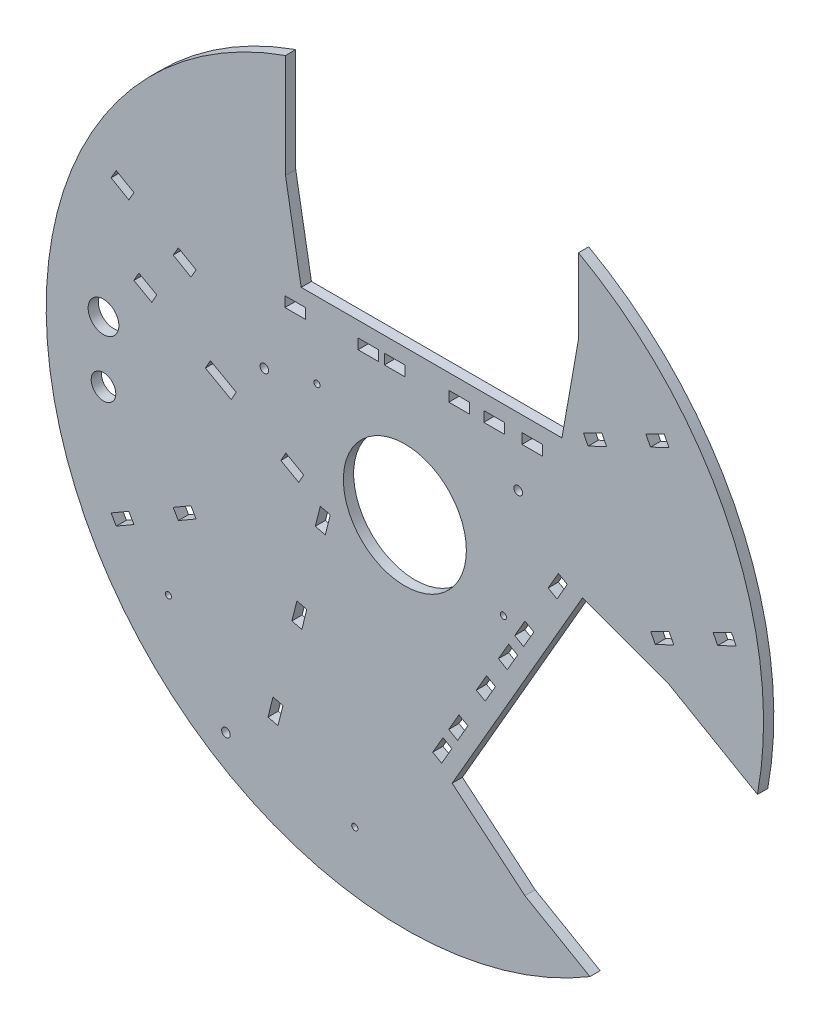
SolidWorks part; units mm, degrees
material "Balsa"
ref_plane "Plan de face" through (0, 0, 0) normal (0, 0, 1) x (1, 0, 0)
ref_plane "Plan de dessus" through (0, 0, 0) normal (0, 1, 0) x (1, 0, 0)
ref_plane "Plan de droite" through (0, 0, 0) normal (1, 0, 0) x (0, 0, -1)
sketch "Esquisse1" plane through (0, 0, 0) normal (0, 0, 1) x (1, 0, 0)
  circle A0 centre (0, 0) radius 175
  dimension "D1" = 350
extrude "Boss.-Extru.1" add sketch "Esquisse1" along normal blind 5
sketch "Esquisse2" plane through (0, 0, 0) normal (0, 0, -1) x (-1, 0, 0)
  line L0 (58.2408, 114.332) -> (58.2408, 213.8766)
  line L1 (58.2408, 213.8766) -> (-84.6817, 213.8766)
  line L2 (-84.6817, 213.8766) -> (-84.6817, 116.5135)
  line L3 (0, 0) -> (-290.6498, 0) construction
  line L4 (-84.6817, 116.5135) -> (-76.6366, 70.8876)
  line L5 (-76.6366, 70.8876) -> (50.5804, 70.8876)
  line L6 (50.5804, 70.8876) -> (58.2408, 114.332)
  line L7 (-128.1349, -6.728) -> (-214.343, -56.5003)
  line L8 (-214.343, -56.5003) -> (-142.8818, -180.2748)
  line L9 (-142.8818, -180.2748) -> (-58.5628, -131.5932)
  line L10 (-58.5628, -131.5932) -> (-23.0722, -101.8131)
  line L11 (-23.0722, -101.8131) -> (-86.6807, 8.3601)
  line L12 (-86.6807, 8.3601) -> (-128.1349, -6.728)
  point P16 (0, 0)
  point P43 (0, 0)
  dimension "D5" = 142.989
  dimension "D6" = 99.5446
  dimension "D1" = 127.217
  dimension "D2" = 100
  dimension "D3" = 100
  dimension "D4" = 142.9225
  dimension "D7" = 70.8876
  dimension "D8" = 50.5804
  dimension "D10" = 120
  dimension "D9" = 2
extrude "Enlèv. mat.-Extru.1" cut sketch "Esquisse2" against normal blind 5
sketch "Esquisse3" plane through (0, 0, 5) normal (0, 0, 1) x (1, 0, 0)
  line L0 (0, 0) -> (0, 103.8673) construction
  line L1 (-49.3567, -7.7578) -> (-58.0775, -2.8643)
  line L2 (-49.3567, -7.7578) -> (-51.8034, -12.1183)
  line L3 (-58.0775, -2.8643) -> (-60.5243, -7.2247)
  line L4 (-51.8034, -12.1183) -> (-60.5243, -7.2247)
  line L5 (-82.2991, 10.7274) -> (-94.8707, 17.7817)
  line L6 (-82.2991, 10.7274) -> (-84.7459, 6.3669)
  line L7 (-94.8707, 17.7817) -> (-97.3175, 13.4213)
  line L8 (-84.7459, 6.3669) -> (-97.3175, 13.4213)
  line L9 (-121.0332, 32.4625) -> (-129.754, 37.356)
  line L10 (-121.0332, 32.4625) -> (-123.48, 28.1021)
  line L11 (-129.754, 37.356) -> (-132.2008, 32.9956)
  line L12 (-123.48, 28.1021) -> (-132.2008, 32.9956)
  line L13 (-36.4119, -18.1392) -> (-38.8398, -27.84)
  line L14 (-36.4119, -18.1392) -> (-41.2623, -16.9253)
  line L15 (-38.8398, -27.84) -> (-43.6902, -26.6261)
  line L16 (0, 0) -> (104.6701, 42.2895) construction
  line L17 (-41.2623, -16.9253) -> (-43.6902, -26.6261)
  line L18 (-47.8487, -63.8364) -> (-50.2765, -73.5372)
  line L19 (-47.8487, -63.8364) -> (-52.6991, -62.6224)
  line L20 (-50.2765, -73.5372) -> (-55.1269, -72.3233)
  line L21 (-52.6991, -62.6224) -> (-55.1269, -72.3233)
  line L22 (-59.4765, -110.2968) -> (-61.9044, -119.9976)
  line L23 (-59.4765, -110.2968) -> (-64.3269, -109.0829)
  line L24 (-61.9044, -119.9976) -> (-66.7548, -118.7837)
  line L25 (-64.3269, -109.0829) -> (-66.7548, -118.7837)
  line L26 (62.9144, -18.0042) -> (58.5843, -15.5042)
  line L27 (62.9144, -18.0042) -> (57.9144, -26.6645)
  line L28 (58.5843, -15.5042) -> (53.5843, -24.1645)
  line L29 (57.9144, -26.6645) -> (53.5843, -24.1645)
  line L30 (39.8511, -47.9511) -> (44.1813, -50.4511)
  line L31 (39.8511, -47.9511) -> (34.8511, -56.6113)
  line L32 (44.1813, -50.4511) -> (39.1813, -59.1113)
  line L33 (34.8511, -56.6113) -> (39.1813, -59.1113)
  line L34 (18.5843, -84.7863) -> (22.9144, -87.2863)
  line L35 (18.5843, -84.7863) -> (13.5843, -93.4465)
  line L36 (22.9144, -87.2863) -> (17.9144, -95.9465)
  line L37 (13.5843, -93.4465) -> (17.9144, -95.9465)
  line L38 (23.0722, -101.8131) -> (86.6807, 8.3601) construction
  line L40 (67.1551, 63.3876) -> (57.1551, 63.3876)
  line L41 (67.1551, 63.3876) -> (67.1551, 58.3876)
  line L42 (67.1551, 58.3876) -> (57.1551, 58.3876)
  line L43 (57.1551, 63.3876) -> (57.1551, 58.3876)
  line L44 (-12.8449, 63.3876) -> (-22.8449, 63.3876)
  line L45 (-12.8449, 63.3876) -> (-12.8449, 58.3876)
  line L46 (-12.8449, 58.3876) -> (-22.8449, 58.3876)
  line L47 (-22.8449, 63.3876) -> (-22.8449, 58.3876)
  line L48 (31.4441, 63.3876) -> (21.4441, 63.3876)
  line L49 (31.4441, 63.3876) -> (31.4441, 58.3876)
  line L50 (31.4441, 58.3876) -> (21.4441, 58.3876)
  line L51 (21.4441, 63.3876) -> (21.4441, 58.3876)
  line L52 (76.6366, 70.8876) -> (-50.5804, 70.8876) construction
  line B0 (122.1484, 6.3102) -> (119.9636, 10.8076)
  line B1 (128.9584, 15.1772) -> (119.9636, 10.8076)
  line B2 (131.1432, 10.6797) -> (122.1484, 6.3102)
  line B3 (131.1432, 10.6797) -> (128.9584, 15.1772)
  line B4 (159.3791, 29.9551) -> (150.3842, 25.5855)
  line B5 (152.569, 21.0881) -> (150.3842, 25.5855)
  line B6 (161.5639, 25.4577) -> (159.3791, 29.9551)
  line B7 (161.5639, 25.4577) -> (152.569, 21.0881)
  line B8 (126.6073, 97.4163) -> (117.6125, 93.0467)
  line B9 (126.6073, 97.4163) -> (128.7921, 92.9189)
  line B10 (117.6125, 93.0467) -> (119.7973, 88.5493)
  line B11 (128.7921, 92.9189) -> (119.7973, 88.5493)
  line B12 (96.1867, 82.6383) -> (98.3714, 78.1409)
  line B13 (96.1867, 82.6383) -> (87.1918, 78.2688)
  line B14 (98.3714, 78.1409) -> (89.3766, 73.7714)
  line B15 (87.1918, 78.2688) -> (89.3766, 73.7714)
  line B16 (87.1918, 78.2688) -> (104.6701, 42.2895) construction
  dimension "D1" = 112.6276
  dimension "D2" = 68
  dimension "D3" = 5
  dimension "D4" = 5
  dimension "D5" = 30.9185
  dimension "D6" = 7.4
  dimension "D7" = 5
  dimension "D8" = 10
  dimension "D9" = 10
  dimension "D10" = 10
  dimension "D11" = 10
  dimension "D12" = 5
  dimension "D13" = 10
  dimension "D14" = 32.5336
  dimension "D15" = 10
  dimension "D16" = 27.4664
  dimension "D17" = 7.5
  dimension "D18" = 10
sketch_block_instance "Bloc1-1"
sketch_block "Bloc1" parameters "D1"=5, "D2"=23.8202, "D3"=40, "D4"=10, "D5"=10, "D6"=5
extrude "Enlèv. mat.-Extru.2" cut sketch "Esquisse3" against normal blind 10
sketch "Esquisse4" plane through (0, 0, 0) normal (0, 0, -1) x (-1, 0, 0)
  line L0 (42.8627, 33.9844) -> (-48.07, -18.5156) construction
  line L1 (42.8627, 33.9844) -> (115.3627, -91.5893) construction
  line L2 (-48.07, -18.5156) -> (24.43, -144.0893) construction
  line L3 (115.3627, -91.5893) -> (24.43, -144.0893) construction
  line L4 (-23.0722, -101.8131) -> (-86.6807, 8.3601) construction
  circle A0 centre (115.3627, -91.5893) radius 1.5
  circle A1 centre (24.43, -144.0893) radius 1.5
  circle A2 centre (-48.07, -18.5156) radius 1.5
  circle A3 centre (42.8627, 33.9844) radius 1.5
  dimension "D1" = 3
  dimension "D2" = 105
  dimension "D3" = 145
  dimension "D4" = 20
  dimension "D5" = 8
extrude "Enlèv. mat.-Extru.3" cut sketch "Esquisse4" against normal blind 10
sketch "Esquisse5" plane through (0, 0, 0) normal (0, 0, -1) x (-1, 0, 0)
  line L0 (132.1784, -70.1252) -> (134.6784, -65.7951)
  line L1 (132.1784, -70.1252) -> (140.8387, -75.1252)
  line L2 (134.6784, -65.7951) -> (143.3387, -70.7951)
  line L3 (140.8387, -75.1252) -> (143.3387, -70.7951)
  line L4 (110.5278, -57.6252) -> (113.0278, -53.2951)
  line L5 (110.5278, -57.6252) -> (101.8675, -52.6252)
  line L6 (113.0278, -53.2951) -> (104.3675, -48.2951)
  line L7 (101.8675, -52.6252) -> (104.3675, -48.2951)
  line L8 (134.6784, 65.7951) -> (132.1784, 70.1252)
  line L9 (134.6784, 65.7951) -> (143.3387, 70.7951)
  line L10 (132.1784, 70.1252) -> (140.8387, 75.1252)
  line L11 (143.3387, 70.7951) -> (140.8387, 75.1252)
  line L12 (110.5278, 57.6252) -> (113.0278, 53.2951)
  line L13 (110.5278, 57.6252) -> (101.8675, 52.6252)
  line L14 (113.0278, 53.2951) -> (104.3675, 48.2951)
  line L15 (101.8675, 52.6252) -> (104.3675, 48.2951)
  line L16 (134.6784, 65.7951) -> (113.0278, 53.2951) construction
  line L17 (143.3387, 70.7951) -> (104.3675, 48.2951) construction
  line L18 (143.3387, -70.7951) -> (104.3675, -48.2951) construction
  dimension "D1" = 10
  dimension "D2" = 115
  dimension "D3" = 25
  dimension "D4" = 25
  dimension "D5" = 5
  dimension "D6" = 115
extrude "Enlèv. mat.-Extru.4" cut sketch "Esquisse5" against normal blind 10
sketch "Esquisse6" plane through (0, 0, 5) normal (0, 0, 1) x (1, 0, 0)
  line L0 (20.7319, -91.0665) -> (84.2319, 18.9187) construction
  line L1 (25.7319, -82.4063) -> (30.7319, -73.746)
  line L2 (25.7319, -82.4063) -> (21.4018, -79.9063)
  line L3 (30.7319, -73.746) -> (26.4018, -71.246)
  line L4 (21.4018, -79.9063) -> (26.4018, -71.246)
  line L5 (49.9819, -40.4041) -> (54.9819, -31.7438)
  line L6 (49.9819, -40.4041) -> (45.6518, -37.9041)
  line L7 (54.9819, -31.7438) -> (50.6518, -29.2438)
  line L8 (45.6518, -37.9041) -> (50.6518, -29.2438)
  line L9 (52.4819, -36.0739) -> (43.8216, -31.0739) construction
  line L10 (58.5, 63.3876) -> (-68.5, 63.3876) construction
  line L11 (48.5, 63.3876) -> (38.5, 63.3876)
  line L12 (48.5, 63.3876) -> (48.5, 58.3876)
  line L14 (74.9018, 12.7584) -> (69.9018, 4.0982)
  line L15 (74.2319, 1.5982) -> (69.9018, 4.0982)
  line L16 (79.2319, 10.2584) -> (74.9018, 12.7584)
  line L17 (79.2319, 10.2584) -> (74.2319, 1.5982)
  line L20 (57.9144, -26.6645) -> (62.9144, -18.0042) construction
  line L21 (38.5, 63.3876) -> (38.5, 58.3876)
  line L22 (48.5, 58.3876) -> (38.5, 58.3876)
  line L23 (0, 63.3876) -> (-10, 63.3876)
  line L24 (0, 63.3876) -> (0, 58.3876)
  line L25 (-10, 63.3876) -> (-10, 58.3876)
  line L26 (0, 58.3876) -> (-10, 58.3876)
  line L27 (-5, 63.3876) -> (-5, 53.3876) construction
  line L29 (-58.5, 58.3876) -> (-48.5, 58.3876)
  line L30 (-48.5, 63.3876) -> (-48.5, 58.3876)
  line L31 (-58.5, 63.3876) -> (-58.5, 58.3876)
  line L32 (-58.5, 63.3876) -> (-48.5, 63.3876)
  line L33 (67.1551, 63.3876) -> (57.1551, 63.3876) construction
  dimension "D1" = 127
  dimension "D2" = 10
  dimension "D3" = 10
  dimension "D4" = 5
  dimension "D5" = 5
  dimension "D6" = 10
  dimension "D7" = 127
  dimension "D8" = 10
  dimension "D9" = 10
  dimension "D10" = 5
  dimension "D11" = 10
  dimension "D12" = 5
extrude "Enlèv. mat.-Extru.5" cut sketch "Esquisse6" against normal blind 5
hole_wizard "Trou taraudé M51" positions "Esquisse8" profile "Esquisse9" tap size "M5" standard "ISO" end condition through all
sketch "Esquisse8" plane through (0, 0, -85) normal (0, 0, -1) x (1, 0, 0)
  point P0 (-68.569, -27.6625)
  point P2 (55.2809, -37.9834)
  point P4 (-87.2993, 135.5593)
sketch "Esquisse9" plane through (-68.569, 27.6625, -85) normal (1, 0, 0) x (0, 1, 0)
  line L0 (0, 0) -> (0, 90)
  line L1 (0, 90) -> (2.1, 90)
  line L2 (2.1, 90) -> (2.1, 0)
  line L3 (2.1, 0) -> (0, 0)
  line L4 (0, -6.35) -> (0, 107.95) construction
  dimension "Diamètre principal du filetage" = 4.2
  dimension "Profondeur du trou pour taraudage jusqu'au prochain" = 90
sketch "Esquisse10" plane through (0, 0, 5) normal (0, 0, 1) x (1, 0, 0)
  circle A0 centre (0, 0) radius 30
  circle A1 centre (-147.0421, -19.3351) radius 6
  circle A2 centre (-147.0421, 10.1871) radius 7.5
extrude "Enlèv. mat.-Extru.6" cut sketch "Esquisse10" against normal blind 5
